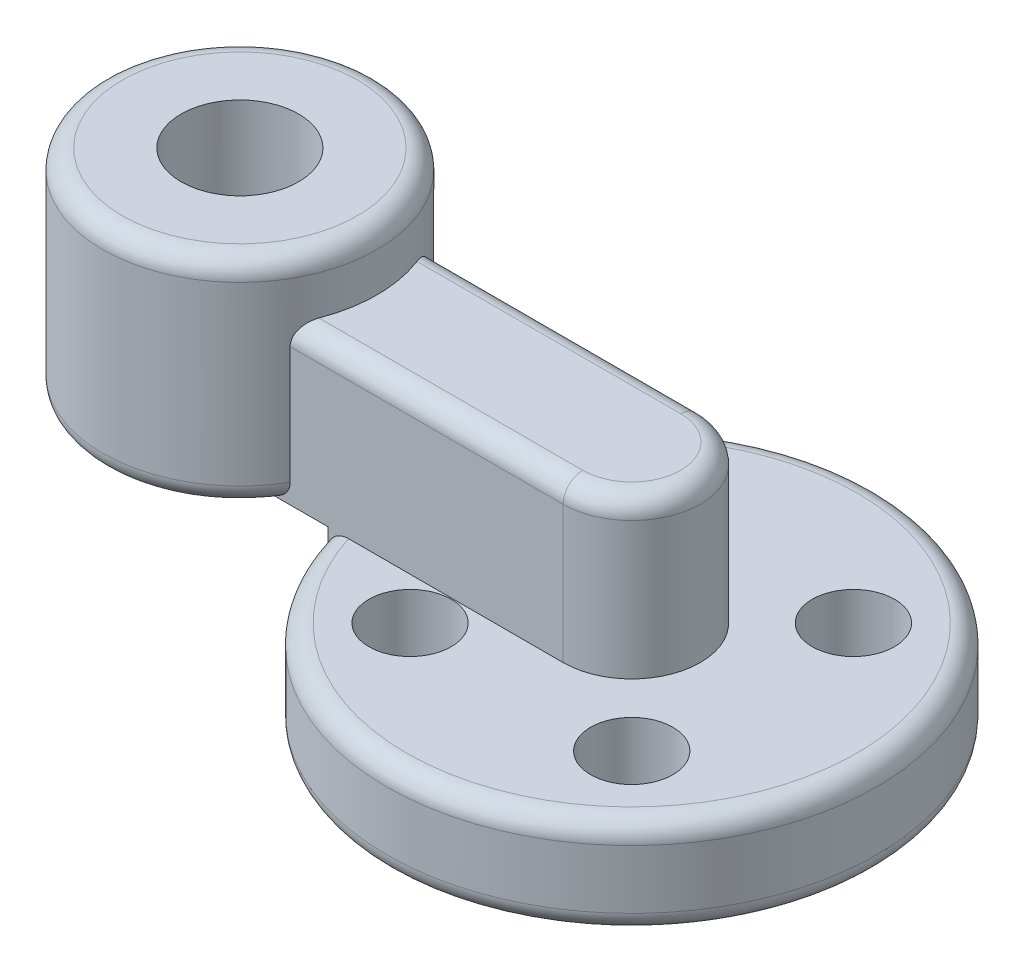
SolidWorks part; units mm, degrees
ref_plane "前视基准面" through (0, 0, 0) normal (0, 0, 1) x (1, 0, 0)
ref_plane "上视基准面" through (0, 0, 0) normal (0, 1, 0) x (1, 0, 0)
ref_plane "右视基准面" through (0, 0, 0) normal (1, 0, 0) x (0, 0, -1)
sketch "草图1" plane through (0, 0, 0) normal (0, 1, 0) x (1, 0, 0)
  circle A0 centre (0, 0) radius 12.5
  dimension "D1" = 25
extrude "凸台-拉伸1" add sketch "草图1" along normal blind 5
sketch "草图2" plane through (0, 5, 0) normal (0, 1, 0) x (1, 0, 0)
  line L0 (0, 0) -> (-20, 0) construction
  line L1 (0, -3.5) -> (-20, -3.5)
  line L2 (0, 3.5) -> (-20, 3.5)
  arc A1 (0, -3.5) -> (0, 3.5) centre (0, 0) ccw
  arc A2 (-20, 3.5) -> (-20, -3.5) centre (-20, 0) ccw
  point P2 (-10, 0)
  dimension "D2" = 3.5
  dimension "D1" = 20
extrude "凸台-拉伸2" add sketch "草图2" along normal blind 8
sketch "草图3" plane through (0, 5, 0) normal (0, 1, 0) x (1, 0, 0)
  line L0 (-5.6569, 5.6569) -> (0, 0) construction
  line L1 (0, 0) -> (0, 8) construction
  circle A0 centre (0, 0) radius 8 construction
  circle A1 centre (-5.6569, 5.6569) radius 1.1
  dimension "D1" = 16
  dimension "D3" = 2.2
  dimension "D2" = 45
extrude "切除-拉伸1" cut sketch "草图3" against normal through all
pattern_circular "阵列(圆周)1" count 4 over 360 about axis through (0, 5, 0) along (0, 1, 0) of "切除-拉伸1"
sketch "草图4" plane through (0, 5, 0) normal (0, 1, 0) x (1, 0, 0)
  circle A0 centre (-5.6569, 5.6569) radius 2.1
  dimension "D1" = 4.2
extrude "切除-拉伸2" cut sketch "草图4" against normal blind 3
pattern_circular "阵列(圆周)2" count 4 over 360 about axis through (0, 5, 0) along (0, -1, 0) of "切除-拉伸2"
sketch "草图5" plane through (0, 13, 0) normal (0, 1, 0) x (1, 0, 0)
  circle A0 centre (-20, 0) radius 7
  dimension "D1" = 14
extrude "凸台-拉伸3" add sketch "草图5" along normal blind 3 and the other way up to surface (8 mm away) other way up to face at (-17, 5, 0)
sketch "草图6" plane through (0, 16, 0) normal (0, 1, 0) x (1, 0, 0)
  circle A0 centre (-20, 0) radius 3
  dimension "D1" = 6
extrude "切除-拉伸3" cut sketch "草图6" against normal through all
sketch "草图7" plane through (0, 5, 0) normal (0, -1, 0) x (1, 0, 0)
  circle A0 centre (-20, 0) radius 5.25
  dimension "D1" = 10.5
extrude "切除-拉伸4" cut sketch "草图7" against normal blind 6
fillet "圆角1" radius 1 6 edges at (-6.9689, 13, -3.5) (3.5, 13, 0) (0, 0, 12.5) (-27, 5, 0) (-6.9689, 13, 3.5) (-20, 16, 7)
fillet "圆角2" radius 1 1 edges at (12.5, 5, 0)
